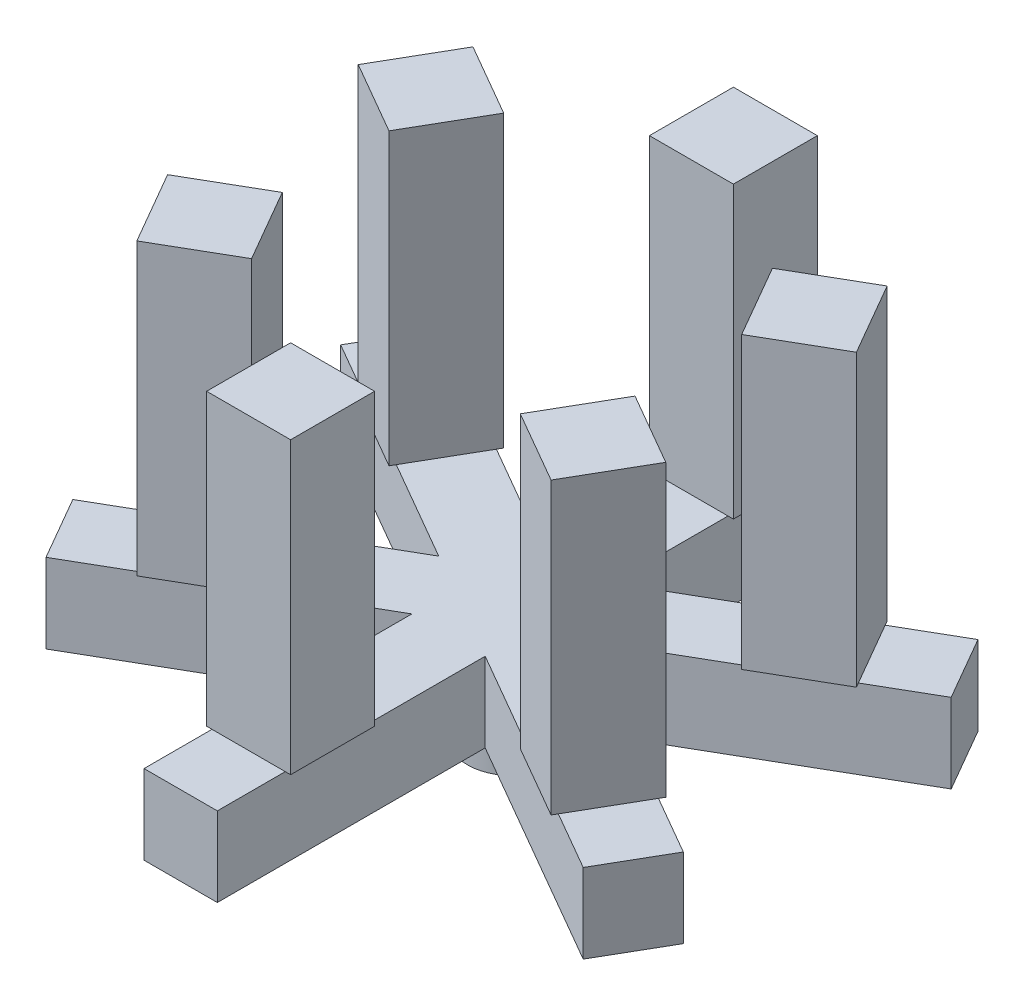
SolidWorks part; units mm, degrees
ref_plane "Front Plane" through (0, 0, 0) normal (0, 0, 1) x (1, 0, 0)
ref_plane "Top Plane" through (0, 0, 0) normal (0, 1, 0) x (1, 0, 0)
ref_plane "Right Plane" through (0, 0, 0) normal (1, 0, 0) x (0, 0, -1)
sketch "Sketch1" plane through (0, 0, 0) normal (0, 1, 0) x (1, 0, 0)
  circle A0 centre (0, 0) radius 29
  dimension "D1" = 58
extrude "Boss-Extrude1" add sketch "Sketch1" along normal blind 28
sketch "Sketch2" plane through (0, 28, 0) normal (0, 1, 0) x (1, 0, 0)
  line L0 (33.3093, 0) -> (-34.6167, 0) construction
  line L1 (24, 0) -> (24, 174)
  line L2 (24, 174) -> (-24, 174)
  line L3 (24, 0) -> (24, -217)
  line L4 (24, -217) -> (-24, -217)
  line L5 (0, 206.6402) -> (0, -315.687) construction
  line L6 (-24, 0) -> (-24, 174)
  line L7 (-24, 0) -> (-24, -217)
  point P10 (-0.6537, 206.6402)
  point P11 (0, 174)
  point P12 (0, -217)
  point P13 (0, 174)
  point P15 (0, 174)
  point P17 (0, -217)
  dimension "D1" = 217
  dimension "D2" = 174
  dimension "D3" = 24
extrude "Boss-Extrude2" add sketch "Sketch2" along normal blind 52
sketch "Sketch3" plane through (0, 80, 0) normal (0, 1, 0) x (1, 0, 0)
  line L0 (0, 0) -> (0, -287.3484) construction
  line L1 (-24, -217) -> (24, -217) construction
  line L2 (-27.5, -172.5) -> (27.5, -172.5)
  line L3 (-27.5, -172.5) -> (-27.5, -117.5)
  line L4 (-27.5, -117.5) -> (27.5, -117.5)
  line L5 (27.5, -172.5) -> (27.5, -117.5)
  line L6 (-27.5, -172.5) -> (27.5, -117.5) construction
  line L7 (-27.5, -117.5) -> (27.5, -172.5) construction
  point P3 (0, -145)
  dimension "D1" = 55
  dimension "D2" = 55
  dimension "D3" = 72
extrude "Boss-Extrude3" add sketch "Sketch3" along normal blind 190
ref_axis "Axis1" through (0, 28, 0) along (0, -1, 0)
pattern_circular "CirPattern1" count 6 every 60 about axis through (0, 28, 0) along (0, -1, 0) of "Boss-Extrude2", "Boss-Extrude3"
